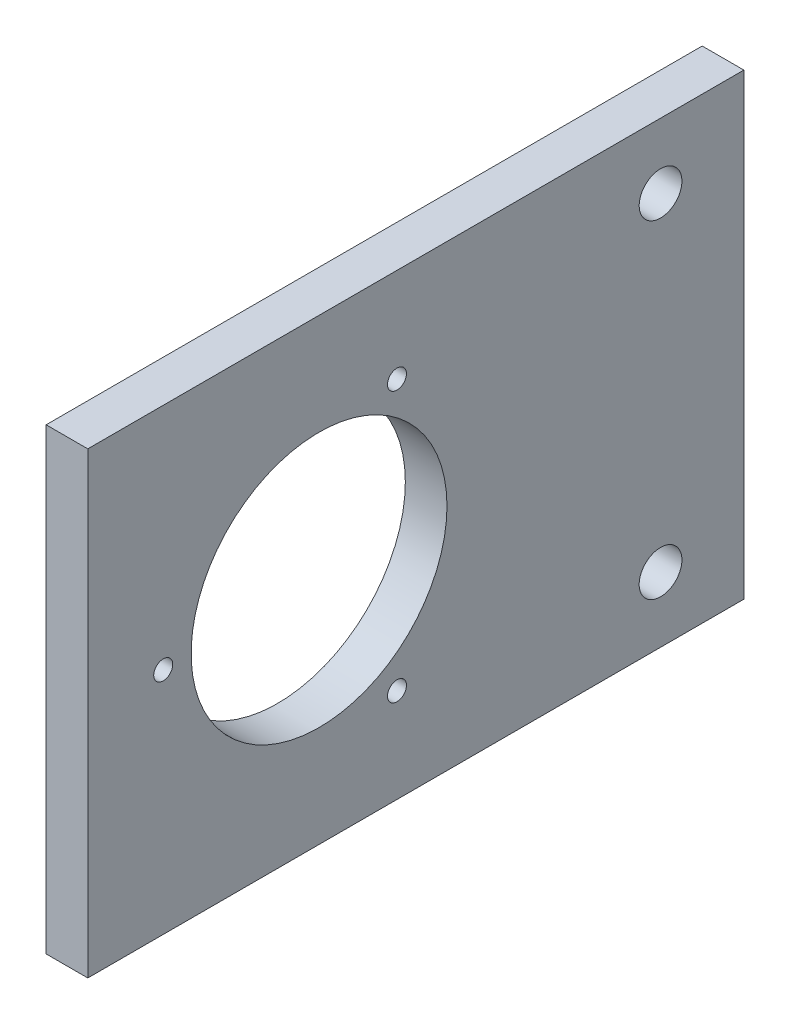
SolidWorks part; units mm, degrees
ref_plane "Front Plane" through (0, 0, 0) normal (1, 0, 0) x (0, 1, 0)
ref_plane "Top Plane" through (0, 0, 0) normal (0, 0, 1) x (0, 1, 0)
ref_plane "Right Plane" through (0, 0, 0) normal (0, 1, 0) x (-1, 0, 0)
sketch "Sketch1" plane through (0, 0, 0) normal (1, 0, 0) x (0, 1, 0)
  line L0 (-34.925, 14.75) -> (34.925, 14.75) construction
  line L1 (-34.925, -50) -> (34.925, -50)
  line L2 (-34.925, -50) -> (-34.925, 50)
  line L3 (-34.925, 50) -> (34.925, 50)
  line L4 (34.925, -50) -> (34.925, 50)
  line L5 (-34.925, -50) -> (34.925, 50) construction
  line L6 (-34.925, 50) -> (34.925, -50) construction
  line L7 (0, 50) -> (0, -50) construction
  line L8 (-34.925, -37.3) -> (34.925, -37.3) construction
  line L9 (0, 14.75) -> (0, 38.5) construction
  line L10 (20.5681, 2.875) -> (0, 14.75) construction
  line L11 (0, 14.75) -> (-20.5681, 2.875) construction
  line L12 (-34.925, -24.6) -> (34.925, -24.6) construction
  circle A5 centre (0, 14.75) radius 19.5
  circle A6 centre (-25, -37.3) radius 3.2576
  circle A7 centre (25, -37.3) radius 3.2576
  circle A8 centre (-20.5681, 2.875) radius 1.45
  circle A9 centre (20.5681, 2.875) radius 1.45
  circle A10 centre (0, 38.5) radius 1.45
  point P0 (0, 0)
  dimension "D5" = 2.9
  dimension "D4" = 23.75
  dimension "D6" = 120
  dimension "D8" = 39
  dimension "D10" = 6.5151
  dimension "D1" = 100
  dimension "D2" = 69.85
  dimension "D3" = 64.75
  dimension "D7" = 120
  dimension "D9" = 12.7
  dimension "D11" = 25
  dimension "D12" = 25.4
extrude "Boss-Extrude1" add sketch "Sketch1" along normal blind 6.35
